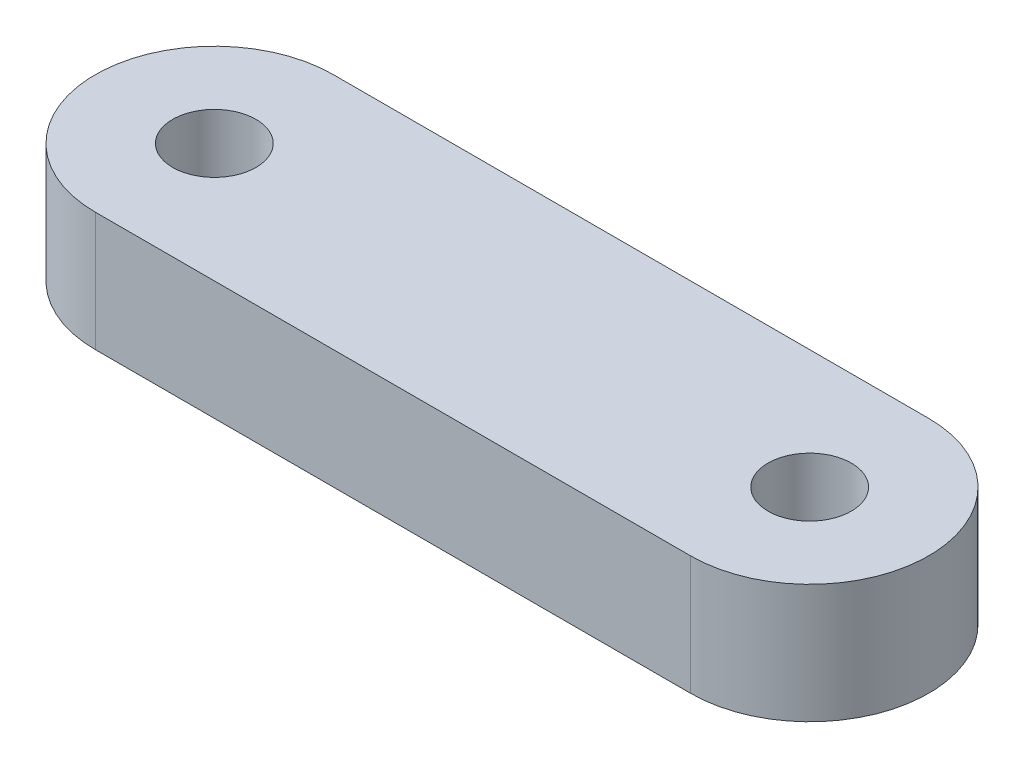
SolidWorks part; units mm, degrees
ref_plane "Front Plane" through (0, 0, 0) normal (0, 0, 1) x (1, 0, 0)
ref_plane "Top Plane" through (0, 0, 0) normal (0, 1, 0) x (1, 0, 0)
ref_plane "Right Plane" through (0, 0, 0) normal (1, 0, 0) x (0, 0, -1)
sketch "Sketch1" plane through (0, 0, 0) normal (0, 1, 0) x (1, 0, 0)
  line L0 (-25, 0) -> (25, 0) construction
  line L1 (-25, 10) -> (25, 10)
  line L2 (-25, -10) -> (25, -10)
  arc A0 (-25, 10) -> (-25, -10) centre (-25, 0) ccw
  arc A1 (25, -10) -> (25, 10) centre (25, 0) ccw
  circle A2 centre (-25, 0) radius 3.5
  circle A3 centre (25, 0) radius 3.5
  point P2 (0, 0)
  dimension "D3" = 7
  dimension "D4" = 7
  dimension "D1" = 20
  dimension "D2" = 50
extrude "Boss-Extrude1" add sketch "Sketch1" along normal blind 10 contours A2 | A3 | L2 A1 L1 A0 region at (-25, 0, 0) region at (25, 0, 0)
